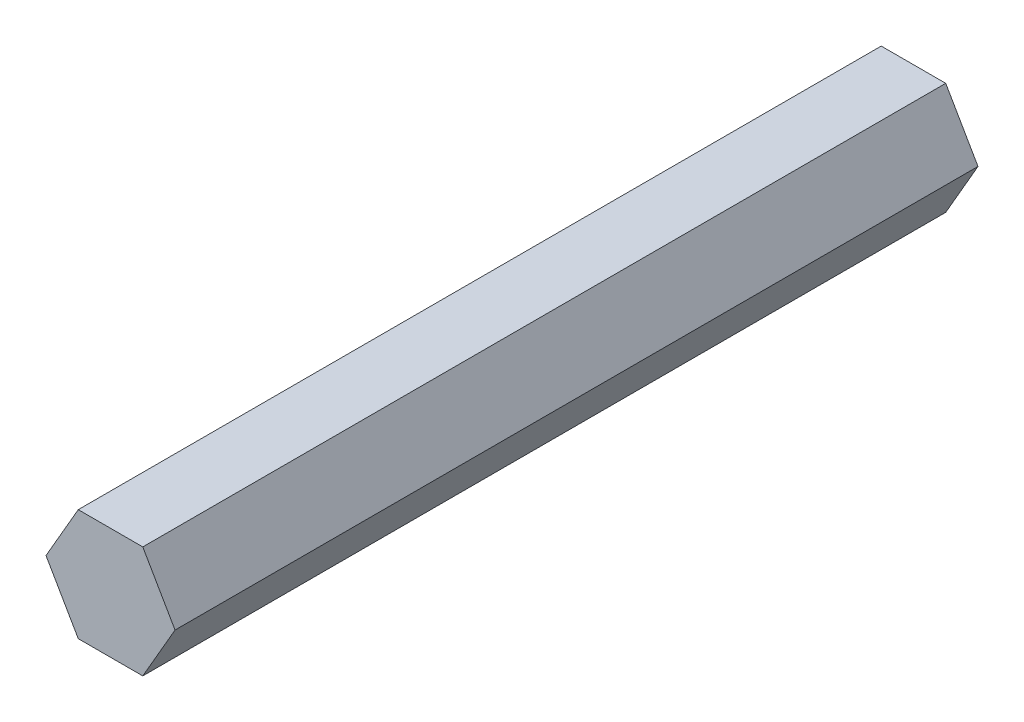
SolidWorks part; units mm, degrees
ref_plane "Front Plane" through (0, 0, 0) normal (0, 0, 1) x (1, 0, 0)
ref_plane "Top Plane" through (0, 0, 0) normal (0, 1, 0) x (1, 0, 0)
ref_plane "Right Plane" through (0, 0, 0) normal (1, 0, 0) x (0, 0, -1)
sketch "Sketch1" plane through (0, 0, 0) normal (0, 0, 1) x (1, 0, 0)
  line L1 (7.3323, 0) -> (3.6662, 6.35)
  line L2 (3.6662, 6.35) -> (-3.6662, 6.35)
  line L3 (-3.6662, 6.35) -> (-7.3323, 0)
  line L4 (-7.3323, 0) -> (-3.6662, -6.35)
  line L5 (-3.6662, -6.35) -> (3.6662, -6.35)
  line L6 (3.6662, -6.35) -> (7.3323, 0)
  circle A0 centre (0, 0) radius 6.35 construction
extrude "Boss-Extrude1" add sketch "Sketch1" along normal blind 91.25
